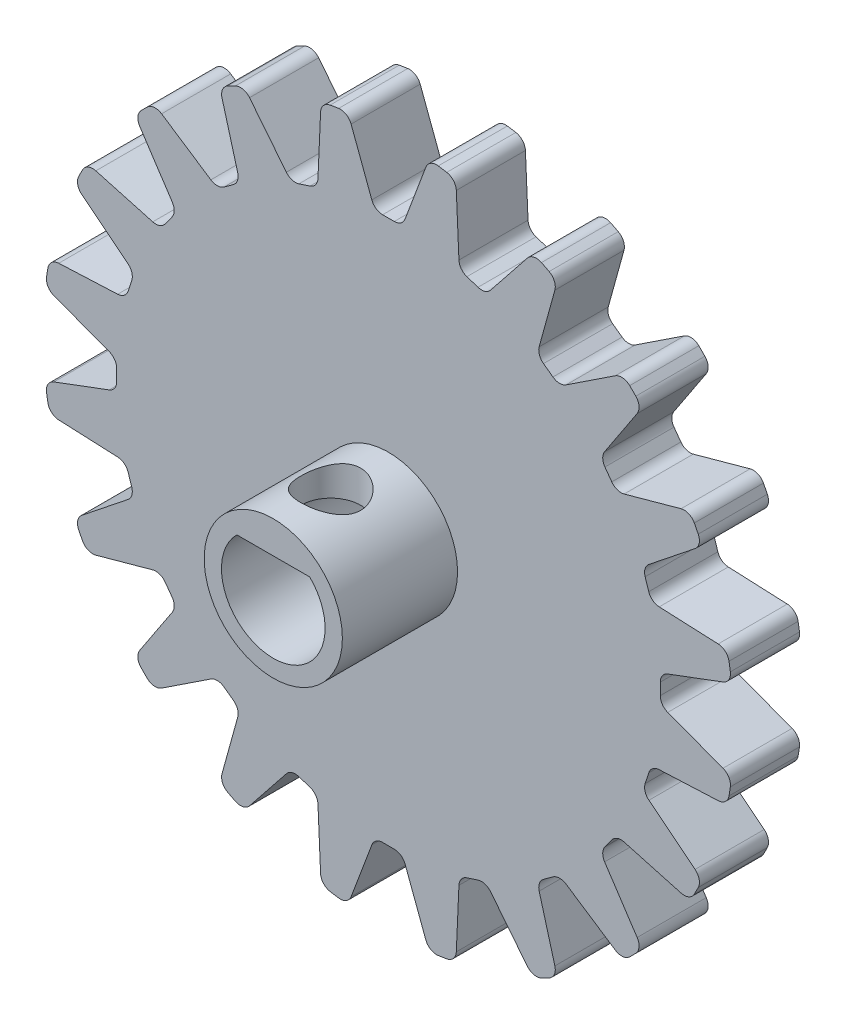
SolidWorks part; units mm, degrees
ref_plane "Front Plane" through (0, 0, 0) normal (0, 0, 1) x (1, 0, 0)
ref_plane "Top Plane" through (0, 0, 0) normal (0, 1, 0) x (1, 0, 0)
ref_plane "Right Plane" through (0, 0, 0) normal (1, 0, 0) x (0, 0, -1)
sketch "Sketch1" plane through (0, 0, 0) normal (0, 0, 1) x (1, 0, 0)
  circle A0 centre (0, 0) radius 15
  dimension "D1" = 30
extrude "Boss-Extrude1" add sketch "Sketch1" along normal blind 3
sketch "Sketch2" plane through (0, 0, 3) normal (0, 0, 1) x (1, 0, 0)
  line L0 (0, 0) -> (0, 15) construction
  line L1 (1.8, 15) -> (-1.8, 15)
  line L2 (-1.8, 15) -> (-0.6, 11.8)
  line L3 (-0.6, 11.8) -> (0.6, 11.8)
  line L4 (1.8, 15) -> (0.6, 11.8)
  circle A0 centre (0, 0) radius 15 construction
  point P10 (0, 11.8)
  dimension "D1" = 0.6
  dimension "D2" = 1.8
  dimension "D3" = 3.2
extrude "Cut-Extrude1" cut sketch "Sketch2" against normal blind 5
pattern_circular "CirPattern1" count 20 every 18 about axis through (0, 0, 3) along (0, 0, 1) of "Cut-Extrude1"
fillet "Fillet1" radius 0.5 80 edges at (9.1937, 7.4213, 1.5) (9.8991, 6.4505, 1.5) (13.0865, 7.331, 1.5) (13.623, 6.2781, 1.5) (11.0371, 4.217, 1.5) (11.4079, 3.0758, 1.5) (14.7114, 2.9283, 1.5) (14.8963, 1.7611, 1.5) (11.8, 0.6, 1.5) (11.8, -0.6, 1.5) (14.8963, -1.7611, 1.5) (14.7114, -2.9283, 1.5) (11.4079, -3.0758, 1.5) (11.0371, -4.217, 1.5) (13.623, -6.2781, 1.5) (13.0865, -7.331, 1.5) (9.8991, -6.4505, 1.5) (9.1937, -7.4213, 1.5) (11.0162, -10.1806, 1.5) (10.1806, -11.0162, 1.5) (7.4213, -9.1937, 1.5) (6.4505, -9.8991, 1.5) (7.331, -13.0865, 1.5) (6.2781, -13.623, 1.5) (4.217, -11.0371, 1.5) (3.0758, -11.4079, 1.5) (2.9283, -14.7114, 1.5) (1.7611, -14.8963, 1.5) (0.6, -11.8, 1.5) (-0.6, -11.8, 1.5) (-1.7611, -14.8963, 1.5) (-2.9283, -14.7114, 1.5) (-3.0758, -11.4079, 1.5) (-4.217, -11.0371, 1.5) (-6.2781, -13.623, 1.5) (-7.331, -13.0865, 1.5) (-6.4505, -9.8991, 1.5) (-7.4213, -9.1937, 1.5) (-10.1806, -11.0162, 1.5) (-11.0162, -10.1806, 1.5) (-9.1937, -7.4213, 1.5) (-9.8991, -6.4505, 1.5) (-13.0865, -7.331, 1.5) (-13.623, -6.2781, 1.5) (-11.0371, -4.217, 1.5) (-11.4079, -3.0758, 1.5) (-14.7114, -2.9283, 1.5) (-14.8963, -1.7611, 1.5) (-11.8, -0.6, 1.5) (-11.8, 0.6, 1.5) (-14.8963, 1.7611, 1.5) (-14.7114, 2.9283, 1.5) (-11.4079, 3.0758, 1.5) (-11.0371, 4.217, 1.5) (-13.623, 6.2781, 1.5) (-13.0865, 7.331, 1.5) (-9.8991, 6.4505, 1.5) (-9.1937, 7.4213, 1.5) (-11.0162, 10.1806, 1.5) (-10.1806, 11.0162, 1.5) (-7.4213, 9.1937, 1.5) (-6.4505, 9.8991, 1.5) (-7.331, 13.0865, 1.5) (-4.217, 11.0371, 1.5) (-3.0758, 11.4079, 1.5) (-2.9283, 14.7114, 1.5) (-1.7611, 14.8963, 1.5) (-0.6, 11.8, 1.5) (0.6, 11.8, 1.5) (1.7611, 14.8963, 1.5) (2.9283, 14.7114, 1.5) (3.0758, 11.4079, 1.5) (4.217, 11.0371, 1.5) (6.2781, 13.623, 1.5) (7.331, 13.0865, 1.5) (6.4505, 9.8991, 1.5) (7.4213, 9.1937, 1.5) (10.1806, 11.0162, 1.5) (11.0162, 10.1806, 1.5) (-6.2781, 13.623, 1.5)
sketch "Sketch3" plane through (0, 0, 3) normal (0, 0, 1) x (1, 0, 0)
  circle A0 centre (0, 0) radius 3
  dimension "D1" = 6
extrude "Boss-Extrude2" add sketch "Sketch3" along normal blind 5
sketch "Sketch11" plane through (0, 0, 0) normal (0, 0, -1) x (-1, 0, 0)
  circle A0 centre (0, 0) radius 3.3388
extrude "Boss-Extrude3" add sketch "Sketch11" along normal blind 1.5
sketch "Sketch4" plane through (0, 0, 0) normal (0, 0, -1) x (-1, 0, 0)
  line L0 (0, 0) -> (0, 1.6) construction
  line L1 (-1.5819, 1.6) -> (1.5819, 1.6)
  arc A0 (-1.5819, 1.6) -> (1.5819, 1.6) centre (0, 0) ccw
  dimension "D1" = 4.5
  dimension "D2" = 1.6
  dimension "D3" = 1.6
extrude "Cut-Extrude2" cut sketch "Sketch4" against normal up to next and the other way blind 1.5 contours A0 L1
ref_plane "Plane1" through (0, 3, 0) normal (0, 1, 0) x (1, 0, 0)
sketch "Sketch5" plane through (0, 3, 0) normal (0, 1, 0) x (1, 0, 0)
  line L0 (-3, -3) -> (3, -3) construction
  line L1 (-1.5819, -8) -> (-1.5819, 1.5) construction
  line L2 (-0.0058, -8) -> (-0.0058, -3) construction
  line L3 (-3, -8) -> (3, -8) construction
  point P0 (-0.0058, -5.5)
  dimension "D1" = 2.5
  dimension "D2" = 1.5761
sketch "Sketch10" plane through (0, 3, 0) normal (0, 1, 0) x (1, 0, 0)
  circle A0 centre (-0.0058, -5.5) radius 1.3
  dimension "D1" = 2.6
extrude "Cut-Extrude3" cut sketch "Sketch10" against normal blind 3
